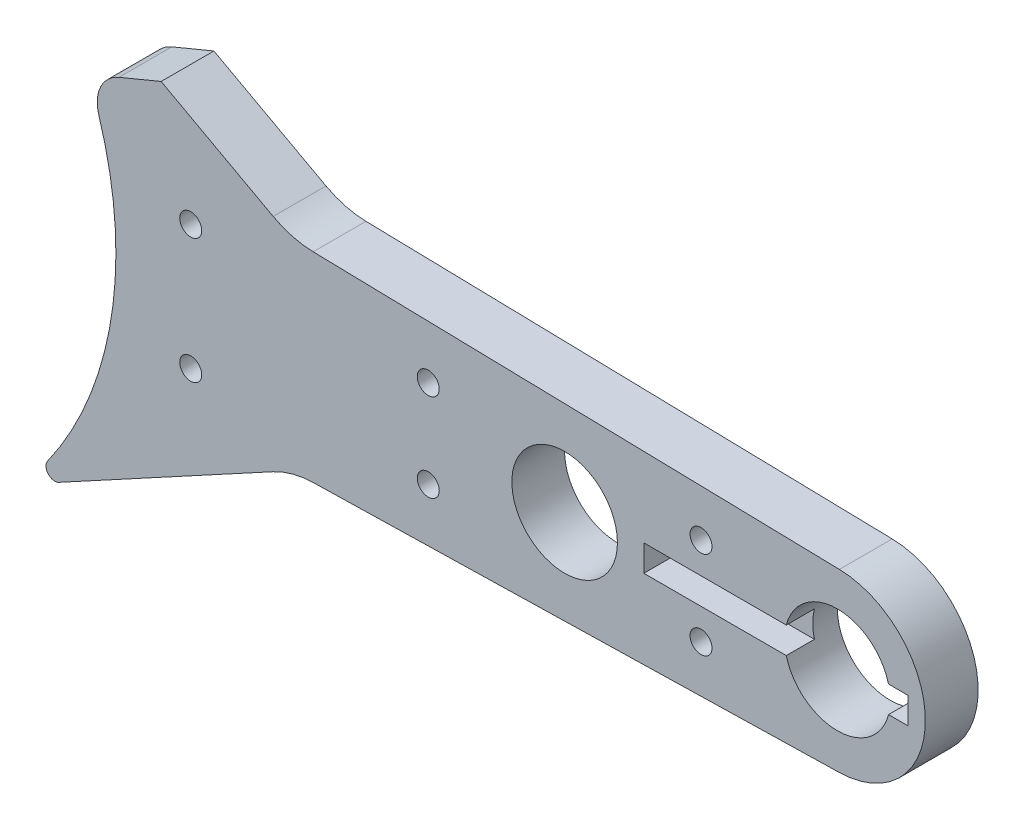
SolidWorks part; units mm, degrees
material "POM copolymère d'acétal"
ref_plane "Front Plane" through (0, 0, 0) normal (0, 0, 1) x (1, 0, 0)
ref_plane "Top Plane" through (0, 0, 0) normal (0, 1, 0) x (1, 0, 0)
ref_plane "Right Plane" through (0, 0, 0) normal (1, 0, 0) x (0, 0, -1)
sketch "Sketch1" plane through (0, 0, 0) normal (0, 0, 1) x (1, 0, 0)
  line L0 (18.0278, 6) -> (62.1135, 4.9987)
  line L1 (18.0278, -6) -> (62.1135, -4.9987)
  line L2 (18.0278, 6) -> (18.0278, -6) construction
  circle A0 centre (0, 0) radius 14
  arc A1 (18.0278, 6) -> (18.0278, -6) centre (0, 0) ccw
  circle A2 centre (46.5, 0) radius 3
  circle A3 centre (62, 0) radius 3
  arc A4 (62.1135, -4.9987) -> (62.1135, 4.9987) centre (62, 0) ccw
  circle A5 centre (0, 0) radius 16.5 construction
  dimension "D1" = 2.5
  dimension "D4" = 6
  dimension "D3" = 2.5
  dimension "D5" = 62
  dimension "D7" = 5
  dimension "D8" = 33
  dimension "D2" = 15.5
  dimension "D6" = 12
extrude "Boss-Extrude1" add sketch "Sketch1" along normal blind 3
hole_wizard "M1.6 Clearance Hole2" positions "Sketch5" profile "Sketch4" hole size "M1.6" standard "DIN"
sketch "Sketch5" plane through (0, 0, 3) normal (0, 0, 1) x (1, 0, 0)
  circle A0 centre (0, 0) radius 16.5
  point P0 (0, 16.5)
  dimension "D1" = 33
sketch "Sketch4" plane through (0, 16.5, 3) normal (1, 0, 0) x (0, -1, 0)
  line L0 (0, 0) -> (0, 11.5)
  line L1 (0, 11.5) -> (0.9, 11.5)
  line L2 (0.9, 11.5) -> (0.9, 0)
  line L5 (0.9, 0) -> (0, 0)
  line L10 (0, 11.5) -> (-0.9, 11.5) construction
  line L11 (0, -6.35) -> (0, 107.95) construction
  dimension "Hole Dia." = 1.8
  dimension "Hole Depth" = 11.5
  dimension "Drill Angle" = 180
pattern_circular "CirPattern1" count 12 over 360 about axis through (0, 0, 3) along (0, 0, -1) of "M1.6 Clearance Hole2"
hole_wizard "Trou taraudé M1.61" positions "Sketch7" profile "Sketch6" tap size "M1.6" standard "Iso" end condition through all
sketch "Sketch7" plane through (0, 0, 3) normal (0, 0, 1) x (1, 0, 0)
  line L6 (0, 0) -> (62, 0) construction
  line L8 (46.5, 0) -> (46.5, -10.138) construction
  line L10 (62, 0) -> (62, -7.973) construction
  line L12 (54.25, -2.5) -> (38.75, -2.5)
  line L13 (54.25, -2.5) -> (54.25, 2.5)
  line L14 (54.25, 2.5) -> (38.75, 2.5)
  line L15 (38.75, -2.5) -> (38.75, 2.5)
  line L16 (54.25, -2.5) -> (38.75, 2.5) construction
  line L17 (54.25, 2.5) -> (38.75, -2.5) construction
  point P283 (38.75, 2.5)
  point P285 (54.25, -2.5)
  point P407 (38.75, -2.5)
  point P409 (54.25, 2.5)
  dimension "D1" = 5
  dimension "D2" = 15.5
sketch "Sketch6" plane through (38.75, 2.5, 3) normal (1, 0, 0) x (0, -1, 0)
  line L0 (0, 0) -> (0, 3)
  line L1 (0, 3) -> (0.625, 3)
  line L2 (0.625, 3) -> (0.625, 0)
  line L5 (0.625, 0) -> (0, 0)
  line L11 (0, -6.35) -> (0, 107.95) construction
  dimension "Diamètre principal du filetage" = 1.25
  dimension "Profondeur du trou pour taraudage jusqu'au prochain" = 3
chamfer "Chamfer2" distance 7 angle 45 2 edges at (18.0278, -6, 1.5) (18.0278, 6, 1.5) first distance on face at (-0.4861, 0, 1.5)
sketch "Esquisse1" plane through (0, 0, 0) normal (0, 0, -1) x (-1, 0, 0)
  circle A0 centre (0, 0) radius 21
  dimension "D1" = 42
extrude "Enlèv. mat.-Extru.1" cut sketch "Esquisse1" against normal blind 10
sketch "Esquisse3" plane through (0, 0, 0) normal (0, 0, -1) x (-1, 0, 0)
  line L0 (0, 0) -> (-25.5, 0) construction
  line L1 (0, 0) -> (-25.2518, 3.5489) construction
  line L2 (0, 0) -> (-25.2518, -3.5489) construction
  circle A0 centre (0, 0) radius 21.5 construction
  circle A1 centre (0, 0) radius 25.5 construction
  circle A2 centre (-25.2518, 3.5489) radius 0.625
  circle A3 centre (-25.2518, -3.5489) radius 0.625
  dimension "D1" = 43
  dimension "D4" = 1.25
  dimension "D5" = 1.25
  dimension "D6" = 4
  dimension "D2" = 8
  dimension "D3" = 8
extrude "Enlèv. mat.-Extru.2" cut sketch "Esquisse3" against normal through all
sketch "Esquisse5" plane through (0, 0, 3) normal (0, 0, 1) x (1, 0, 0)
  line L1 (51, 0.75) -> (66, 0.75)
  line L2 (51, 0.75) -> (51, -0.75)
  line L3 (51, -0.75) -> (66, -0.75)
  line L4 (66, 0.75) -> (66, -0.75)
  circle A0 centre (62, 0) radius 3 construction
  dimension "D1" = 0.75
  dimension "D2" = 1.5
  dimension "D3" = 4
  dimension "D4" = 15
extrude "Enlèv. mat.-Extru.3" cut sketch "Esquisse5" against normal blind 1.6
sketch "Esquisse9" plane through (0, 0, 3) normal (0, 0, 1) x (1, 0, 0)
  line L0 (22.5, 9.2966) -> (19.4097, 8.0165)
  line L1 (29.6111, 5.7369) -> (17.3049, 11.8971) construction
  line L2 (62, 0) -> (46.5, 0) construction
  line L3 (22.5, 9.2966) -> (17.3049, 11.8971)
  arc A0 (19.4097, 8.0165) -> (17.3049, 11.8971) centre (0, 0) ccw
  arc A1 (17.3049, -11.8971) -> (17.3049, 11.8971) centre (0, 0) ccw construction
  dimension "D1" = 22.5
  dimension "D2" = 24
extrude "Enlèv. mat.-Extru.4" cut sketch "Esquisse9" against normal blind 10
fillet "Congé1" radius 2 1 edges at (19.4097, 8.0165, 1.5)
sketch "Esquisse10" plane through (0, 0, 3) normal (0, 0, 1) x (1, 0, 0)
  line L0 (31, 5.7054) -> (23.5698, 9.7397)
  line L1 (62.1135, 4.9987) -> (29.6111, 5.7369) construction
  line L2 (22.5, 9.2966) -> (23.5698, 9.7397)
  line L4 (62, 0) -> (46.5, 0) construction
  line L5 (21.1752, 8.7478) -> (22.5, 9.2966) construction
  line L7 (31, 5.7054) -> (31, -5.7054) construction
  line L8 (29.6111, -5.7369) -> (62.1135, -4.9987) construction
  line L9 (22.5, 9.2966) -> (29.6111, 5.7369)
  line L10 (29.6111, 5.7369) -> (31, 5.7054)
  line L11 (31, -5.7054) -> (29.6111, -5.7369)
  line L12 (29.6111, -5.7369) -> (17.3049, -11.8971)
  line L13 (31, -5.7054) -> (15.5851, -14.075)
  arc A0 (17.3049, -11.8971) -> (15.5851, -14.075) centre (0, 0) cw
  dimension "D1" = 28.5
  dimension "D2" = 15.5
  dimension "D3" = 28.5
extrude "Boss.-Extru.1" add sketch "Esquisse10" against normal blind 3
fillet "Congé2" radius 5 2 edges at (31, 5.7054, 1.5) (31, -5.7054, 1.5)
fillet "Congé3" radius 0.5 1 edges at (15.5851, -14.075, 1.5)
